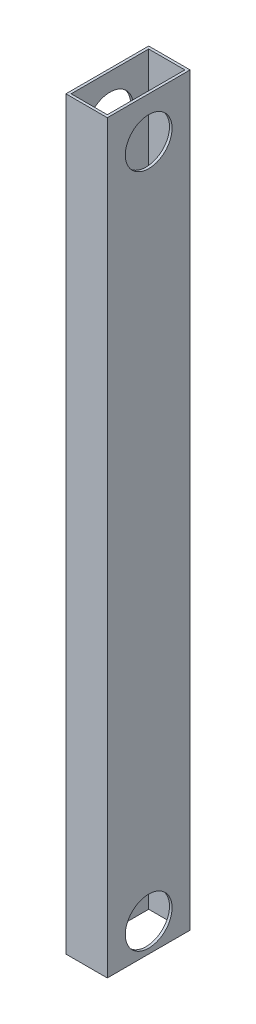
SolidWorks part; units mm, degrees
ref_plane "Front Plane" through (0, 0, 0) normal (0, 0, 1) x (1, 0, 0)
ref_plane "Top Plane" through (0, 0, 0) normal (0, 1, 0) x (1, 0, 0)
ref_plane "Right Plane" through (0, 0, 0) normal (1, 0, 0) x (0, 0, -1)
sketch "Sketch1" plane through (0, 0, 0) normal (0, 1, 0) x (1, 0, 0)
  line L1 (0, 0) -> (25.4, 0)
  line L2 (0, 0) -> (0, 50.8)
  line L3 (0, 50.8) -> (25.4, 50.8)
  line L4 (25.4, 0) -> (25.4, 50.8)
  dimension "D1" = 50.8
  dimension "D2" = 25.4
extrude "Extrude-Thin1" add sketch "Sketch1" along normal blind 457.2 thin thin type one direction reverse wall 1.5875
sketch "Sketch2" plane through (25.4, 0, 0) normal (1, 0, 0) x (0, 0, -1)
  line L0 (0, 0) -> (50.8, 0) construction
  line L1 (50.8, 457.2) -> (50.8, 0) construction
  line L2 (0, 457.2) -> (50.8, 457.2) construction
  circle A0 centre (25.4, 17.526) radius 14.351
  circle A1 centre (25.4, 431.8) radius 14.351
  dimension "D1" = 17.526
  dimension "D2" = 28.702
  dimension "D6" = 28.702
  dimension "D3" = 25.4
  dimension "D4" = 25.4
  dimension "D5" = 25.4
extrude "Cut-Extrude1" cut sketch "Sketch2" against normal through all
